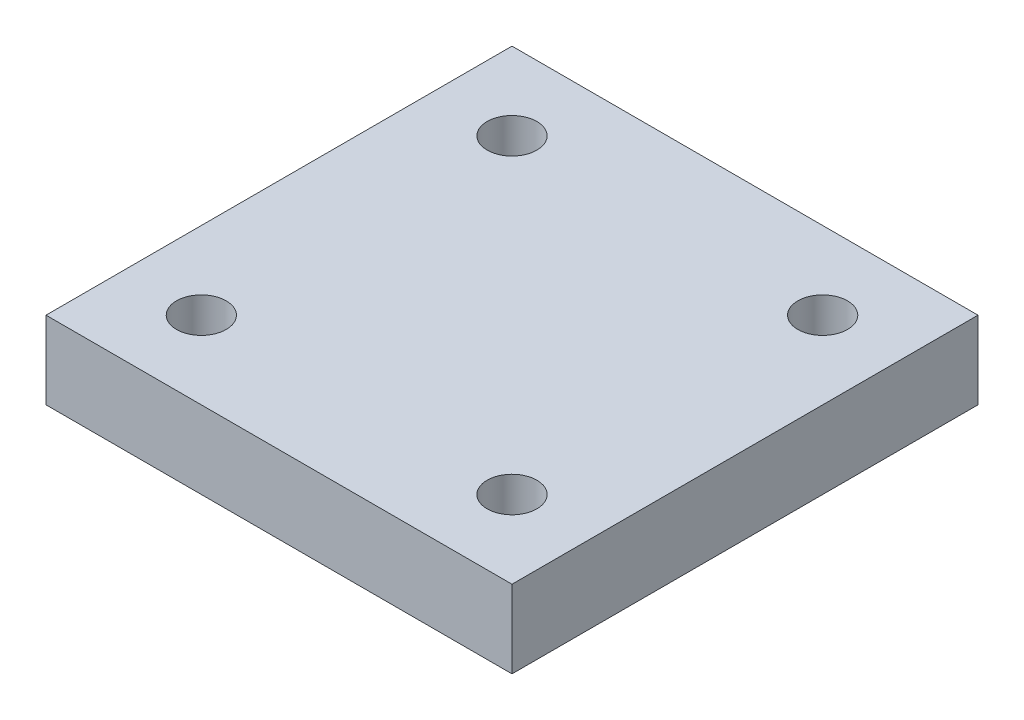
SolidWorks part; units mm, degrees
ref_plane "Front Plane" through (0, 0, 0) normal (0, 0, 1) x (1, 0, 0)
ref_plane "Top Plane" through (0, 0, 0) normal (0, 1, 0) x (1, 0, 0)
ref_plane "Right Plane" through (0, 0, 0) normal (1, 0, 0) x (0, 0, -1)
sketch "Sketch1" plane through (0, 0, 0) normal (0, 1, 0) x (1, 0, 0)
  line L1 (-15, 15) -> (15, 15)
  line L2 (-15, 15) -> (-15, -15)
  line L3 (-15, -15) -> (15, -15)
  line L4 (15, 15) -> (15, -15)
  line L5 (-15, 15) -> (15, -15) construction
  line L6 (-15, -15) -> (15, 15) construction
  circle A0 centre (-10, 10) radius 1.6
  circle A1 centre (10, 10) radius 1.6
  circle A2 centre (10, -10) radius 1.6
  circle A3 centre (-10, -10) radius 1.6
  point P0 (0, 0)
  dimension "D3" = 5
  dimension "D4" = 5
  dimension "D5" = 3.2
  dimension "D1" = 30
  dimension "D2" = 30
  dimension "D6" = 2
  dimension "D7" = 2
extrude "Boss-Extrude1" add sketch "Sketch1" along normal blind 5
